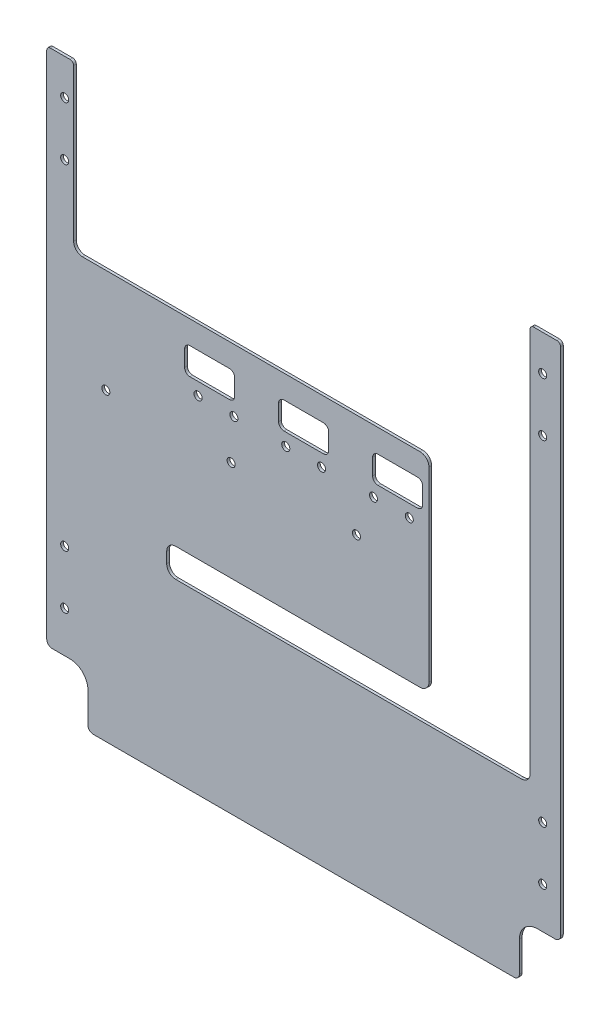
SolidWorks part; units mm, degrees
material "1023 Tôle d'acier au carbone (SS)"
ref_plane "Front" through (0, 0, 0) normal (0, 0, 1) x (1, 0, 0)
ref_plane "Top" through (0, 0, 0) normal (0, 1, 0) x (1, 0, 0)
ref_plane "Right" through (0, 0, 0) normal (1, 0, 0) x (0, 0, -1)
sketch "Esquisse1" plane through (0, 0, 0) normal (0, 0, 1) x (1, 0, 0)
  line L1 (0, 0) -> (287, 0)
  line L2 (0, 0) -> (0, 320)
  line L3 (0, 320) -> (287, 320)
  line L4 (287, 0) -> (287, 320)
  dimension "D1" = 287
  dimension "D2" = 320
extrude "Boss.-Extru.1" add sketch "Esquisse1" along normal blind 1.5
sketch "Esquisse2" plane through (0, 0, 1.5) normal (0, 0, 1) x (1, 0, 0)
  line L0 (143.5, 0) -> (143.5, 56.1801) construction
  line L1 (287, 0) -> (264, 0)
  line L2 (287, 0) -> (287, 30)
  line L3 (287, 30) -> (264, 30)
  line L4 (264, 0) -> (264, 30)
  line L5 (0, 0) -> (287, 0) construction
  line L6 (23, 0) -> (23, 30)
  line L7 (0, 30) -> (23, 30)
  line L8 (0, 0) -> (0, 30)
  line L9 (0, 0) -> (23, 0)
  dimension "D1" = 23
  dimension "D2" = 30
extrude "Enlèv. mat.-Extru.1" cut sketch "Esquisse2" against normal through all both and the other way through all
fillet "Congé1" radius 10 2 edges at (264, 30, 0.75) (23, 30, 0.75)
fillet "Congé2" radius 3 4 edges at (287, 30, 0.75) (0, 30, 0.75) (23, 0, 0.75) (264, 0, 0.75)
sketch "Esquisse3" plane through (0, 0, 1.5) normal (0, 0, 1) x (1, 0, 0)
  line L0 (287, 320) -> (0, 320) construction
  line L1 (73.5, 320) -> (213.5, 320)
  line L2 (73.5, 320) -> (73.5, 228)
  line L3 (73.5, 228) -> (213.5, 228)
  line L4 (213.5, 320) -> (213.5, 228)
  line L5 (143.5, 228) -> (143.5, 0) construction
  line L6 (26, 0) -> (261, 0) construction
  dimension "D1" = 140
  dimension "D2" = 92
extrude "Enlèv. mat.-Extru.2" cut sketch "Esquisse3" against normal through all both and the other way through all
sketch "Esquisse4" plane through (0, 0, 1.5) normal (0, 0, 1) x (1, 0, 0)
  line L0 (287, 320) -> (213.5, 320) construction
  line L1 (213.5, 320) -> (270, 320)
  line L2 (213.5, 320) -> (213.5, 98)
  line L3 (213.5, 98) -> (270, 98)
  line L4 (270, 320) -> (270, 98)
  line L5 (287, 33) -> (287, 320) construction
  line L6 (213.5, 320) -> (213.5, 228) construction
  line L7 (26, 0) -> (261, 0) construction
  dimension "D1" = 17
  dimension "D2" = 98
extrude "Enlèv. mat.-Extru.3" cut sketch "Esquisse4" against normal through all both and the other way through all
sketch "Esquisse5" plane through (0, 0, 1.5) normal (0, 0, 1) x (1, 0, 0)
  line L0 (73.5, 320) -> (0, 320) construction
  line L1 (73.5, 228) -> (15, 228)
  line L2 (73.5, 228) -> (73.5, 320)
  line L3 (73.5, 320) -> (15, 320)
  line L4 (15, 228) -> (15, 320)
  line L5 (0, 320) -> (0, 33) construction
  dimension "D1" = 15
extrude "Enlèv. mat.-Extru.4" cut sketch "Esquisse5" against normal through all both and the other way through all
sketch "Esquisse6" plane through (0, 0, 1.5) normal (0, 0, 1) x (1, 0, 0)
  line L0 (213.5, 98) -> (213.5, 228) construction
  line L1 (213.5, 98) -> (67, 98)
  line L2 (213.5, 98) -> (213.5, 114)
  line L3 (213.5, 114) -> (67, 114)
  line L4 (67, 98) -> (67, 114)
  line L5 (26, 0) -> (261, 0) construction
  line L6 (0, 320) -> (0, 33) construction
  dimension "D1" = 16
  dimension "D2" = 98
  dimension "D3" = 67
extrude "Enlèv. mat.-Extru.5" cut sketch "Esquisse6" against normal through all both and the other way through all
fillet "Congé3" radius 5 6 edges at (270, 98, 0.75) (67, 98, 0.75) (67, 114, 0.75) (213.5, 114, 0.75) (213.5, 228, 0.75) (15, 228, 0.75)
sketch "Esquisse7" plane through (0, 0, 1.5) normal (0, 0, 1) x (1, 0, 0)
  line L0 (277, 320) -> (277, 300) construction
  line L1 (287, 320) -> (270, 320) construction
  line L2 (270, 320) -> (270, 103) construction
  line L3 (277, 300) -> (277, 270) construction
  line L4 (143.5, 0) -> (143.5, 300) construction
  line L5 (26, 0) -> (261, 0) construction
  line L6 (10, 300) -> (10, 270) construction
  line L7 (10, 320) -> (10, 300) construction
  line L8 (0, 176.5) -> (287, 176.5) construction
  line L9 (0, 320) -> (0, 33) construction
  line L10 (287, 33) -> (287, 320) construction
  line L11 (277, 53) -> (277, 83) construction
  line L12 (277, 33) -> (277, 53) construction
  line L13 (10, 33) -> (10, 53) construction
  line L14 (10, 53) -> (10, 83) construction
  line L15 (33, 170) -> (0, 170) construction
  line L16 (33, 170) -> (103, 170) construction
  line L17 (103, 170) -> (103, 182.3786) construction
  circle A0 centre (277, 300) radius 2.25
  circle A1 centre (277, 270) radius 2.25
  circle A2 centre (10, 270) radius 2.25
  circle A3 centre (10, 300) radius 2.25
  circle A4 centre (277, 83) radius 2.25
  circle A5 centre (277, 53) radius 2.25
  circle A6 centre (10, 53) radius 2.25
  circle A7 centre (10, 83) radius 2.25
  circle A8 centre (33, 170) radius 2.25
  circle A9 centre (103, 170) radius 2.25
  circle A10 centre (173, 170) radius 2.25
  point P40 (0, 159.4933)
  dimension "D2" = 4.5
  dimension "D4" = 30
  dimension "D6" = 33
  dimension "D1" = 7
  dimension "D3" = 20
  dimension "D5" = 70
  dimension "D7" = 170
extrude "Enlèv. mat.-Extru.6" cut sketch "Esquisse7" against normal through all both and the other way through all
sketch "Esquisse8" plane through (0, 0, 1.5) normal (0, 0, 1) x (1, 0, 0)
  line L0 (143.5, 0) -> (143.5, 158.346) construction
  line L1 (26, 0) -> (261, 0) construction
  line L2 (208.5, 228) -> (20, 228) construction
  line L3 (182.5, 193) -> (202.5, 193) construction
  line L4 (153.5, 193) -> (182.5, 193) construction
  line L5 (104.5, 193) -> (84.5, 193) construction
  circle A0 centre (133.5, 193) radius 2.25
  circle A1 centre (153.5, 193) radius 2.25
  circle A2 centre (182.5, 193) radius 2.25
  circle A3 centre (202.5, 193) radius 2.25
  circle A4 centre (84.5, 193) radius 2.25
  circle A5 centre (104.5, 193) radius 2.25
  dimension "D1" = 4.5
  dimension "D2" = 20
  dimension "D3" = 35
  dimension "D4" = 20
  dimension "D5" = 39
extrude "Enlèv. mat.-Extru.7" cut sketch "Esquisse8" against normal through all both and the other way through all
sketch "Esquisse9" plane through (0, 0, 1.5) normal (0, 0, 1) x (1, 0, 0)
  line L0 (133.5, 193) -> (153.5, 193) construction
  line L1 (129.5, 215) -> (157.5, 215)
  line L2 (129.5, 215) -> (129.5, 200)
  line L3 (129.5, 200) -> (157.5, 200)
  line L4 (157.5, 215) -> (157.5, 200)
  line L5 (143.5, 193) -> (143.5, 215) construction
  line L6 (153.5, 193) -> (169.75, 193) construction
  line L7 (169.75, 193) -> (169.75, 205) construction
  line L8 (182, 215) -> (182, 200)
  line L9 (210, 200) -> (182, 200)
  line L10 (210, 215) -> (210, 200)
  line L11 (210, 215) -> (182, 215)
  line L12 (182.5, 193) -> (182.5, 194.1597) construction
  line L13 (104.5, 193) -> (104.5, 194.1597) construction
  line L14 (77, 215) -> (105, 215)
  line L15 (77, 215) -> (77, 200)
  line L16 (77, 200) -> (105, 200)
  line L17 (105, 215) -> (105, 200)
  dimension "D1" = 28
  dimension "D2" = 15
  dimension "D3" = 22
  dimension "D4" = 27.5
extrude "Enlèv. mat.-Extru.8" cut sketch "Esquisse9" against normal through all both and the other way through all
fillet "Congé4" radius 3 12 edges at (157.5, 200, 0.75) (157.5, 215, 0.75) (129.5, 215, 0.75) (129.5, 200, 0.75) (210, 200, 0.75) (210, 215, 0.75) (182, 215, 0.75) (182, 200, 0.75) (105, 200, 0.75) (105, 215, 0.75) (77, 215, 0.75) (77, 200, 0.75)
fillet "Congé6" radius 2 4 edges at (287, 320, 0.75) (270, 320, 0.75) (0, 320, 0.75) (15, 320, 0.75)
